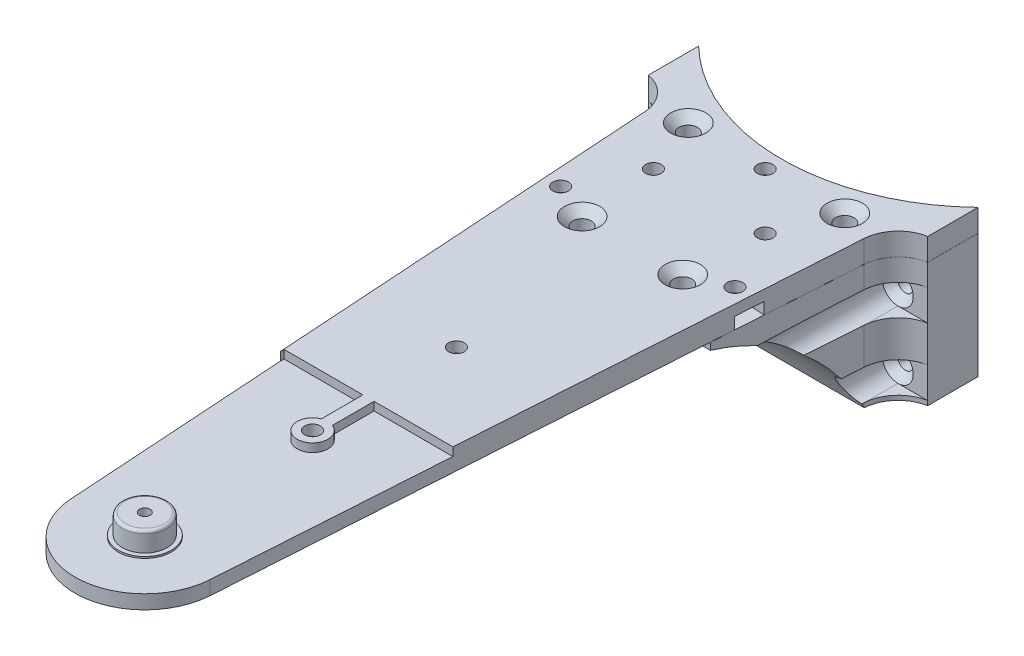
SolidWorks part; units mm, degrees
ref_plane "Front Plane" through (0, 0, 0) normal (0, 0, 1) x (1, 0, 0)
ref_plane "Top Plane" through (0, 0, 0) normal (0, 1, 0) x (1, 0, 0)
ref_plane "Right Plane" through (0, 0, 0) normal (1, 0, 0) x (0, 0, -1)
sketch "Sketch1" plane through (0, 0, 0) normal (0, 1, 0) x (1, 0, 0)
  line L0 (0, 0) -> (0, -150) construction
  line L1 (-22.2029, -1.4463) -> (-12.4736, -150.8125) construction
  line L2 (22.2029, -1.4462) -> (12.4736, -150.8125) construction
  line L3 (-12.4736, -150.8125) -> (-19.6328, -40.9037)
  line L4 (12.4736, -150.8125) -> (19.6328, -40.9037)
  line L5 (-25, -25.9037) -> (25, -25.9037) construction
  line L6 (-25, -25.9037) -> (-25, -34.9037)
  line L7 (25, -25.9037) -> (25, -34.9037)
  circle A0 centre (0, 0) radius 36 construction
  arc A1 (-12.4736, -150.8125) -> (12.4736, -150.8125) centre (0, -150) ccw
  circle A2 centre (0, 0) radius 19.5 construction
  circle A3 centre (0, 19.5) radius 2.75 construction
  circle A4 centre (0, 0) radius 22.25 construction
  arc A5 (-25, -25.9037) -> (25, -25.9037) centre (0, 0) ccw
  arc A6 (-25, -34.9037) -> (-19.6328, -40.9037) centre (-26.1442, -41.3278) cw
  arc A7 (25, -34.9037) -> (19.6328, -40.9037) centre (26.1442, -41.3278) ccw
  dimension "D1" = 72
  dimension "D3" = 25
  dimension "D4" = 39
  dimension "D5" = 5.5
  dimension "D2" = 150
  dimension "D6" = 50
  dimension "D7" = 9
  dimension "D8" = 15
extrude "Boss-Extrude1" add sketch "Sketch1" against normal blind 4
sketch "Sketch2" plane through (0, -4, 0) normal (0, -1, 0) x (1, 0, 0)
  line L0 (25, 34.9037) -> (25, 25.9037) construction
  line L1 (-25, 25.9037) -> (-25, 34.9037) construction
  line L2 (25, 34.9037) -> (25, 25.9037)
  line L3 (-25, 25.9037) -> (-25, 34.9037)
  line L4 (-19.6328, 40.9037) -> (19.6328, 40.9037)
  arc A0 (19.6328, 40.9037) -> (25, 34.9037) centre (26.1442, 41.3278) ccw construction
  arc A1 (25, 25.9037) -> (-25, 25.9037) centre (0, 0) ccw construction
  arc A2 (-25, 34.9037) -> (-19.6328, 40.9037) centre (-26.1442, 41.3278) ccw construction
  arc A3 (19.6328, 40.9037) -> (25, 34.9037) centre (26.1442, 41.3278) ccw
  arc A4 (25, 25.9037) -> (-25, 25.9037) centre (0, 0) ccw
  arc A5 (-25, 34.9037) -> (-19.6328, 40.9037) centre (-26.1442, 41.3278) ccw
extrude "Boss-Extrude2" add sketch "Sketch2" along normal offset from surface (22.2378 mm away) 26.2378 up to face at (0, 0, 65.6223)
ref_plane "Plane1" through (0, 0, 34.9037) normal (0, 0, 1) x (1, 0, 0)
fillet "Fillet2" radius 40 1 edges at (0, -4, 40.9037)
sketch "Sketch3" plane through (0, 0, 34.9037) normal (0, 0, 1) x (1, 0, 0)
  line L0 (25, 0) -> (-25, 0) construction
  line L1 (-19.6636, -22.6878) -> (19.6636, -22.6878) construction
  line L2 (-19.6636, -22.6878) -> (-19.6636, -10.6878) construction
  line L3 (-19.6636, -10.6878) -> (19.6636, -10.6878) construction
  line L4 (19.6636, -22.6878) -> (19.6636, -10.6878) construction
  line L5 (-19.6636, -22.6878) -> (19.6636, -10.6878) construction
  line L6 (-19.6636, -10.6878) -> (19.6636, -22.6878) construction
  line L7 (-19.6636, -7.9378) -> (-25, -7.9378)
  line L8 (-25, -7.9378) -> (-25, -13.4378)
  line L9 (-25, -13.4378) -> (-19.6636, -13.4378)
  line L10 (-25, -26.2378) -> (-25, 0) construction
  line L11 (0, -16.6878) -> (-25, -16.6878) construction
  line L12 (-25, -25.4378) -> (-25, -19.9378)
  line L13 (-25, -19.9378) -> (-19.6636, -19.9378)
  line L14 (-19.6636, -25.4378) -> (-25, -25.4378)
  line L15 (0, -16.6878) -> (0, 0) construction
  line L16 (19.6636, -25.4378) -> (25, -25.4378)
  line L17 (25, -19.9378) -> (19.6636, -19.9378)
  line L18 (25, -25.4378) -> (25, -19.9378)
  line L19 (25, -13.4378) -> (19.6636, -13.4378)
  line L20 (25, -7.9378) -> (25, -13.4378)
  line L21 (19.6636, -7.9378) -> (25, -7.9378)
  arc A0 (-19.6636, -13.4378) -> (-19.6636, -7.9378) centre (-19.6636, -10.6878) ccw
  arc A4 (-19.6636, -19.9378) -> (-19.6636, -25.4378) centre (-19.6636, -22.6878) cw
  arc A5 (19.6636, -19.9378) -> (19.6636, -25.4378) centre (19.6636, -22.6878) ccw
  arc A6 (19.6636, -13.4378) -> (19.6636, -7.9378) centre (19.6636, -10.6878) cw
  point P0 (0, -16.6878)
  dimension "D4" = 5.5
  dimension "D1" = 10.6878
  dimension "D2" = 12
  dimension "D3" = 39.3272
extrude "Cut-Extrude1" cut sketch "Sketch3" along normal through all
chamfer "Chamfer1" [suppressed] distance 2.75 angle 60
hole_wizard "CSK for M2.5 Flat Head Machine Screw1" positions "Sketch5" profile "Sketch6" countersink size "M2.5" standard "ANSI Metric" end condition through all
sketch "Sketch5" plane through (0, 0, 34.9037) normal (0, 0, 1) x (1, 0, 0)
  point P0 (19.6636, -22.6878)
  point P3 (-19.6636, -22.6878)
  point P6 (-19.6636, -10.6878)
  point P9 (19.6636, -10.6878)
sketch "Sketch6" plane through (19.6636, -22.6878, 34.9037) normal (1, 0, 0) x (0, -1, 0)
  line L0 (0, 0) -> (0, 9)
  line L1 (0, 9) -> (1.4, 9)
  line L2 (1.4, 9) -> (1.4, 1.35)
  line L3 (1.4, 1.35) -> (2.75, 0)
  line L5 (2.75, 0) -> (0, 0)
  line L6 (-1.4, 1.35) -> (-2.75, 0) construction
  line L11 (0, -6.35) -> (0, 107.95) construction
  dimension "Thru Hole Dia." = 2.8
  dimension "Thru Hole Depth" = 9
  dimension "Near C'Sink Dia." = 5.5
  dimension "Near C'Sink Angle" = 90
sketch "Sketch8" plane through (0, 0, 0) normal (0, 1, 0) x (1, 0, 0)
  line L1 (1.0164, -92.5616) -> (1.0209, -117.4381) construction
  line L2 (-0.9836, -92.5619) -> (-0.9791, -117.4384) construction
  line L3 (15.1322, -109.9973) -> (15.1322, -176.6324)
  line L4 (15.1322, -176.6324) -> (-15.0896, -176.6324)
  line L5 (-15.0896, -176.6324) -> (-15.0896, -109.9973)
  line L29 (-0.9805, -109.9973) -> (-0.9791, -117.4384)
  line L30 (1.0195, -109.9973) -> (1.0209, -117.4381)
  line L31 (1.0195, -109.9973) -> (15.1322, -109.9973)
  line L72 (-15.0896, -109.9973) -> (-0.9805, -109.9973)
  arc A4 (-0.9791, -117.4384) -> (1.0209, -117.4381) centre (0.0213, -120) ccw construction
  arc A8 (-0.9791, -117.4384) -> (1.0209, -117.4381) centre (0.0213, -120) ccw
  point P0 (0.0213, -176.6324)
  dimension "D2" = 5.5
extrude "Cut-Extrude3" cut sketch "Sketch8" against normal blind 1.5
sketch "Sketch9" plane through (0, -4, 0) normal (0, -1, 0) x (1, 0, 0)
  line L0 (-17.2982, 76.7436) -> (17.2982, 76.7436)
  line L1 (17.2982, 76.7436) -> (17.9496, 66.7436)
  line L2 (17.9496, 66.7436) -> (-17.9496, 66.7436)
  line L3 (-17.9496, 66.7436) -> (-17.2982, 76.7436)
  line L4 (-17.2982, 76.7436) -> (-12.4736, 150.8125) construction
  line L5 (12.4736, 150.8125) -> (17.2982, 76.7436) construction
  dimension "D1" = 10
extrude "Cut-Extrude4" cut sketch "Sketch9" along normal through all
sketch "Sketch11" plane through (0, -4, 0) normal (0, -1, 0) x (1, 0, 0)
  circle A0 centre (0, 0) radius 161
extrude "Cut-Extrude5" cut sketch "Sketch11" along normal blind 0.01
sketch "Sketch12" plane through (0, 0, 0) normal (0, 1, 0) x (1, 0, 0)
  line L0 (-17.9496, -66.7436) -> (17.9496, -66.7436) construction
  line L1 (-17.9496, -66.7436) -> (17.9496, -66.7436) construction
  line L3 (-9, -62.7436) -> (9, -62.7436) construction
  line L4 (-9, -62.7436) -> (-14, -38.7436) construction
  line L5 (-14, -38.7436) -> (14, -38.7436) construction
  line L6 (9, -62.7436) -> (14, -38.7436) construction
  line L7 (-9, -62.7436) -> (14, -38.7436) construction
  line L8 (-14, -38.7436) -> (9, -62.7436) construction
  circle A0 centre (-14, -38.7436) radius 1.65
  circle A1 centre (14, -38.7436) radius 1.65
  circle A2 centre (-9, -62.7436) radius 1.65
  circle A3 centre (9, -62.7436) radius 1.65
  point P2 (0, -53.3523)
  point P15 (0, -62.7436)
  dimension "D1" = 3.3
  dimension "D2" = 4
  dimension "D3" = 28
  dimension "D4" = 24
  dimension "D5" = 18
extrude "Cut-Extrude6" cut sketch "Sketch12" against normal blind 8.25
ref_plane "Plane2" through (0, -5.2702, 0) normal (0, 1, 0) x (1, 0, 0)
sketch "Sketch13" plane through (0, -5.2702, 0) normal (0, 1, 0) x (1, 0, 0)
  line L0 (0, 0) -> (0, -36) construction
  line L1 (-11.75, -59.9936) -> (-6.25, -59.9936)
  line L2 (-11.75, -59.9936) -> (-11.75, -65.4936)
  line L3 (-11.75, -65.4936) -> (-6.25, -65.4936) construction
  line L4 (-6.25, -59.9936) -> (-6.25, -65.4936)
  line L5 (-11.75, -59.9936) -> (-6.25, -65.4936) construction
  line L6 (-11.75, -65.4936) -> (-6.25, -59.9936) construction
  line L7 (-6.25, -65.4936) -> (-6.25, -66.7436)
  line L8 (-17.9496, -66.7436) -> (17.9496, -66.7436) construction
  line L9 (-6.25, -66.7436) -> (-11.75, -66.7436)
  line L10 (-11.75, -66.7436) -> (-11.75, -65.4936)
  line L11 (6.25, -66.7436) -> (11.75, -66.7436)
  line L12 (6.25, -65.4936) -> (6.25, -66.7436)
  line L13 (6.25, -59.9936) -> (6.25, -65.4936)
  line L14 (11.75, -59.9936) -> (6.25, -59.9936)
  line L15 (11.75, -59.9936) -> (11.75, -65.4936)
  line L16 (11.75, -66.7436) -> (11.75, -65.4936)
  arc A0 (-25, -25.9037) -> (25, -25.9037) centre (0, 0) ccw construction
  point P0 (-9, -62.7436)
  dimension "D1" = 5.5
extrude "Cut-Extrude7" cut sketch "Sketch13" against normal blind 8.5
sketch "Sketch14" plane through (0, -8.25, 0) normal (0, 1, 0) x (1, 0, 0)
  line L0 (0, 0) -> (0, -36) construction
  line L1 (-14, -38.7436) -> (0, 0) construction
  line L2 (-15.6518, -35.2228) -> (-10.4791, -37.0919) construction
  line L3 (-15.6518, -35.2228) -> (-17.5209, -40.3954)
  line L4 (-17.5209, -40.3954) -> (-12.3482, -42.2645)
  line L5 (-10.4791, -37.0919) -> (-12.3482, -42.2645)
  line L6 (-15.6518, -35.2228) -> (-12.3482, -42.2645) construction
  line L7 (-17.5209, -40.3954) -> (-10.4791, -37.0919) construction
  line L8 (-15.6518, -35.2228) -> (-14.7849, -32.8239)
  line L9 (-14.7849, -32.8239) -> (-9.6123, -34.693)
  line L10 (-9.6123, -34.693) -> (-10.4791, -37.0919)
  line L11 (14.7849, -32.8239) -> (9.6123, -34.693)
  line L12 (15.6518, -35.2228) -> (14.7849, -32.8239)
  line L13 (15.6518, -35.2228) -> (17.5209, -40.3954)
  line L14 (17.5209, -40.3954) -> (12.3482, -42.2645)
  line L15 (10.4791, -37.0919) -> (12.3482, -42.2645)
  line L16 (9.6123, -34.693) -> (10.4791, -37.0919)
  arc A0 (-25, -25.9037) -> (25, -25.9037) centre (0, 0) ccw construction
  point P6 (-14, -38.7436)
  dimension "D1" = 5.5
extrude "Cut-Extrude8" cut sketch "Sketch14" along normal blind 2
hole_wizard "CSK for M3 Flat Head Machine Screw1" positions "Sketch15" profile "Sketch16" countersink size "M3" standard "ANSI Metric"
sketch "Sketch15" plane through (0, 0, 0) normal (0, 1, 0) x (1, 0, 0)
  point P0 (-14, -38.7436)
  point P3 (14, -38.7436)
  point P6 (9, -62.7436)
  point P9 (-9, -62.7436)
sketch "Sketch16" plane through (-14, 0, 38.7436) normal (1, 0, 0) x (0, 0, 1)
  line L0 (0, 0) -> (0, 8.9914)
  line L1 (0, 8.9914) -> (1.65, 8)
  line L2 (1.65, 8) -> (1.65, 1.5)
  line L3 (1.65, 1.5) -> (3.15, 0)
  line L5 (3.15, 0) -> (0, 0)
  line L6 (-1.65, 1.5) -> (-3.15, 0) construction
  line L10 (0, 8.9914) -> (-1.65, 8) construction
  line L11 (0, -6.35) -> (0, 107.95) construction
  dimension "Hole Dia." = 3.3
  dimension "Hole Depth" = 8
  dimension "Near C'Sink Dia." = 6.3
  dimension "Near C'Sink Angle" = 90
  dimension "Drill Angle" = 118
sketch "Sketch18" plane through (0, -4, 0) normal (0, -1, 0) x (1, 0, 0)
  circle A1 centre (0.0071, 39) radius 2.75
  circle A2 centre (0.0071, 39) radius 2.75 construction
  circle A3 centre (0.0173, 94.25) radius 2.75
  circle A4 centre (0.0173, 94.25) radius 2.75 construction
  arc A5 (1.0209, 117.4381) -> (-0.9791, 117.4384) centre (0.0213, 120) ccw construction
  circle A7 centre (0.0173, 94.25) radius 1.4
  circle A9 centre (-15.5725, 60.0029) radius 1.4
  circle A11 centre (-15.5725, 60.0029) radius 2.75
  circle A12 centre (-15.5725, 60.0029) radius 2.75 construction
  circle A13 centre (15.5944, 59.9971) radius 1.4
  circle A15 centre (0.0071, 39) radius 1.4
  circle A17 centre (15.5944, 59.9971) radius 2.75
  circle A18 centre (15.5944, 59.9971) radius 2.75 construction
  arc A19 (1.0209, 117.4381) -> (-0.9791, 117.4384) centre (0.0213, 120) ccw construction
  circle A20 centre (0.0213, 120) radius 1.4
  dimension "D4" = 2.8
  dimension "D1" = 0
  dimension "D2" = 0
  dimension "D6" = 0
  dimension "D9" = 0
extrude "Cut-Extrude9" cut sketch "Sketch18" against normal through all
sketch "Sketch19" plane through (0, -4, 0) normal (0, -1, 0) x (1, 0, 0)
  line L1 (1.4503, 122.475) -> (-1.4076, 122.475)
  line L2 (-1.4076, 122.475) -> (-2.8366, 120)
  line L3 (-2.8366, 120) -> (-1.4076, 117.525)
  line L4 (-1.4076, 117.525) -> (1.4503, 117.525)
  line L5 (1.4503, 117.525) -> (2.8792, 120)
  line L6 (2.8792, 120) -> (1.4503, 122.475)
  line L7 (1.4462, 96.725) -> (-1.4117, 96.725)
  line L8 (-1.4117, 96.725) -> (-2.8406, 94.25)
  line L9 (-2.8406, 94.25) -> (-1.4117, 91.775)
  line L10 (-1.4117, 91.775) -> (1.4462, 91.775)
  line L11 (1.4462, 91.775) -> (2.8751, 94.25)
  line L12 (2.8751, 94.25) -> (1.4462, 96.725)
  line L13 (-12.7206, 59.8171) -> (-13.9857, 62.3797)
  line L14 (-13.9857, 62.3797) -> (-16.8375, 62.5655)
  line L15 (-16.8375, 62.5655) -> (-18.4243, 60.1886) construction
  line L16 (-18.4243, 60.1886) -> (-17.1593, 57.626) construction
  line L17 (-17.1593, 57.626) -> (-14.3074, 57.4402)
  line L18 (-14.3074, 57.4402) -> (-12.7206, 59.8171)
  line L19 (2.4786, 37.5649) -> (2.4857, 40.4228)
  line L20 (2.4857, 40.4228) -> (0.0143, 41.8579)
  line L21 (0.0143, 41.8579) -> (-2.4643, 40.4351)
  line L22 (-2.4643, 40.4351) -> (-2.4714, 37.5772)
  line L23 (-2.4714, 37.5772) -> (0, 36.1421) construction
  line L24 (0, 36.1421) -> (2.4786, 37.5649) construction
  line L25 (0, 0) -> (0, 162.5) construction
  line L26 (-18.4243, 60.1886) -> (-15.5725, 60.0029) construction
  line L27 (-19.6328, 40.9037) -> (-12.4736, 150.8125) construction
  line L28 (-16.8375, 62.5655) -> (-18.2159, 62.6553)
  line L29 (-18.2159, 62.6553) -> (-18.5377, 57.7158)
  line L30 (-18.5377, 57.7158) -> (-17.1593, 57.626)
  line L31 (18.2159, 62.6553) -> (18.5377, 57.7158)
  line L32 (16.8375, 62.5655) -> (18.2159, 62.6553)
  line L33 (13.9857, 62.3797) -> (16.8375, 62.5655)
  line L34 (12.7206, 59.8171) -> (13.9857, 62.3797)
  line L35 (14.3074, 57.4402) -> (12.7206, 59.8171)
  line L36 (17.1593, 57.626) -> (14.3074, 57.4402)
  line L37 (18.5377, 57.7158) -> (17.1593, 57.626)
  line L38 (-2.4714, 37.5772) -> (-2.4714, 35.9151)
  line L39 (-2.4714, 35.9151) -> (2.4786, 35.9146)
  line L40 (2.4786, 35.9146) -> (2.4786, 37.5649)
  circle A0 centre (0.0213, 120) radius 2.475 construction
  circle A1 centre (0.0173, 94.25) radius 2.475 construction
  circle A2 centre (-15.5725, 60.0029) radius 2.475 construction
  circle A3 centre (0.0071, 39) radius 2.475 construction
  arc A4 (12.4736, 150.8125) -> (-12.4736, 150.8125) centre (0, 150) ccw construction
  arc A5 (25, 25.9037) -> (-25, 25.9037) centre (0, 0) ccw construction
  circle A6 centre (0.0213, 120) radius 1.4 construction
  dimension "D1" = 4.95
extrude "Cut-Extrude10" cut sketch "Sketch19" against normal blind 2.1
sketch "Sketch20" plane through (0, -1.5, 0) normal (0, 1, 0) x (1, 0, 0)
  circle A0 centre (0, -150) radius 4.75
  dimension "D1" = 9.5
extrude "Boss-Extrude3" add sketch "Sketch20" along normal blind 0.3
sketch "Sketch21" plane through (0, -1.2, 0) normal (0, 1, 0) x (1, 0, 0)
  circle A0 centre (0, -150) radius 4
  dimension "D1" = 8
extrude "Boss-Extrude4" add sketch "Sketch21" along normal blind 3.5
fillet "Fillet4" radius 0.5 1 edges at (0, 2.3, 154)
sketch "Sketch22" plane through (0, 0, 0) normal (0, 1, 0) x (1, 0, 0)
  line L0 (0, 0) -> (0, -150) construction
  circle A0 centre (0, 0) radius 50 construction
  arc A1 (-25, -25.9037) -> (25, -25.9037) centre (0, 0) ccw construction
  circle A2 centre (10, -48.9898) radius 1.4
  circle A3 centre (10, -48.9898) radius 3.5 construction
  circle A4 centre (-10, -48.9898) radius 1.4
  dimension "D1" = 100
  dimension "D2" = 2.8
  dimension "D4" = 7
  dimension "D3" = 10
extrude "Cut-Extrude12" cut sketch "Sketch22" against normal through all contours A2 | A4
sketch "Sketch24" plane through (0, -4, 0) normal (0, -1, 0) x (1, 0, 0)
  circle A0 centre (0, 150) radius 0.95
  dimension "D1" = 1.9
extrude "Cut-Extrude13" cut sketch "Sketch24" against normal through all both and the other way through all
ref_plane "Plane3" through (0, 0, 36) normal (0, 0, -1) x (-1, 0, 0)
sketch "Sketch25" plane through (0, 0, 36) normal (0, 0, -1) x (-1, 0, 0)
  line L0 (-19.6636, -22.6878) -> (19.6636, -22.6878) construction
  line L1 (0, 0) -> (0, -22.6878) construction
  line L2 (-14.13, -15.5878) -> (-10.13, -15.5878)
  line L3 (-14.13, -15.5878) -> (-14.13, -18.5878)
  line L4 (-14.13, -18.5878) -> (-10.13, -18.5878)
  line L5 (-10.13, -15.5878) -> (-10.13, -18.5878)
  line L6 (10.13, -15.5878) -> (10.13, -18.5878)
  line L7 (14.13, -18.5878) -> (10.13, -18.5878)
  line L8 (14.13, -15.5878) -> (14.13, -18.5878)
  line L9 (14.13, -15.5878) -> (10.13, -15.5878)
  dimension "D1" = 7.1
  dimension "D2" = 20.26
  dimension "D3" = 4
  dimension "D4" = 3
extrude "Boss-Extrude6" add sketch "Sketch25" along normal blind 3
chamfer "Chamfer2" distance 1.8 angle 45 2 edges at (-12.1512, -18.5878, 33.8873) (12.1512, -18.5878, 33.8873)
